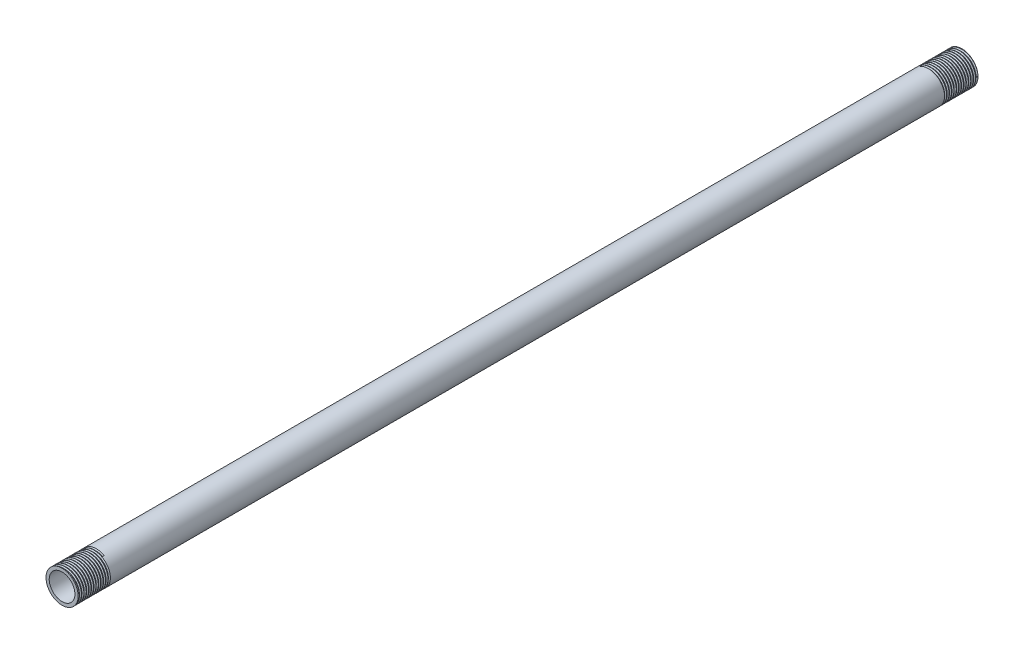
SolidWorks part; units mm, degrees
material "Plain Carbon Steel"
ref_plane "Front Plane" through (0, 0, 0) normal (0, 0, 1) x (1, 0, 0)
ref_plane "Top Plane" through (0, 0, 0) normal (0, 1, 0) x (1, 0, 0)
ref_plane "Right Plane" through (0, 0, 0) normal (1, 0, 0) x (0, 0, -1)
sketch "Sketch1" plane through (0, 0, 0) normal (0, 0, 1) x (1, 0, 0)
  circle A0 centre (0, 0) radius 10
  dimension "D1" = 20
extrude "Boss-Extrude1" add sketch "Sketch1" along normal blind 560
shell "Shell1" thickness 2 removed face at (10, 0, 560) removed face at (10, 0, 0)
thread "Thread1" pitch 1.5 method cut profile "Thread Profile1" start angle 0, offset 0, length 20, pitch 1.5, diameter 20
ref_plane "Plane1" through (10, 0, 0) normal (0, -1, 0) x (1, 0, 0)
sketch "Thread Profile1" plane through (10, 0, 0) normal (0, -1, 0) x (1, 0, 0)
  line L0 (0, 0) -> (0, 1.5) construction
  line L11 (0, 0) -> (0, 1.3125)
  line L12 (0, 1.3125) -> (-0.8119, 0.8437)
  line L13 (-0.8119, 0.8437) -> (-0.8119, 0.4687)
  line L15 (-0.8119, 0.4687) -> (0, 0)
  line L17 (-0.8119, 0.6562) -> (0, 0.6562) construction
  point P2 (0, 0)
  dimension "Pitch" = 1.5
  dimension "Profile_Angle" = 60
  dimension "Profile_Land" = 0.375
  dimension "Profile_Height" = 0.8119
thread "Thread2" pitch 1.5 method cut profile "Thread Profile2" start angle 0, offset 0, length 20, pitch 1.5, diameter 20
ref_plane "Plane2" through (-10, 0, 560) normal (0, -1, 0) x (-1, 0, 0)
sketch "Thread Profile2" plane through (-10, 0, 560) normal (0, -1, 0) x (-1, 0, 0)
  line L0 (0, 0) -> (0, 1.5) construction
  line L11 (0, 0) -> (0, 1.3125)
  line L12 (0, 1.3125) -> (-0.8119, 0.8437)
  line L13 (-0.8119, 0.8437) -> (-0.8119, 0.4687)
  line L15 (-0.8119, 0.4687) -> (0, 0)
  line L17 (-0.8119, 0.6562) -> (0, 0.6562) construction
  point P2 (0, 0)
  dimension "Pitch" = 1.5
  dimension "Profile_Angle" = 60
  dimension "Profile_Land" = 0.375
  dimension "Profile_Height" = 0.8119
